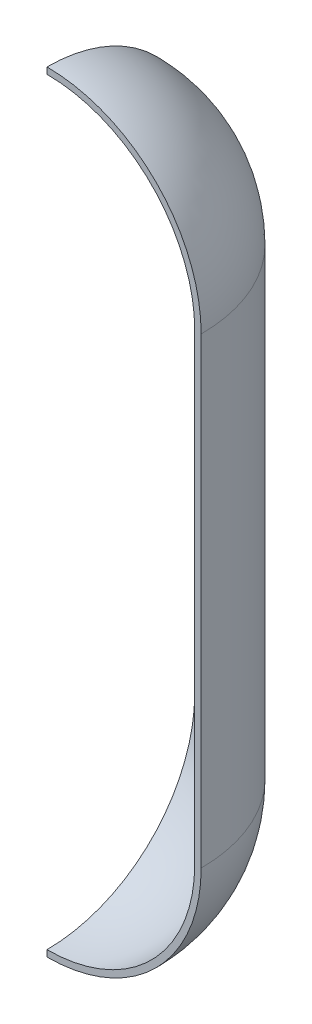
SolidWorks part; units mm, degrees
ref_plane "Front" through (0, 0, 0) normal (0, 0, 1) x (1, 0, 0)
ref_plane "Top" through (0, 0, 0) normal (0, 1, 0) x (1, 0, 0)
ref_plane "Right" through (0, 0, 0) normal (1, 0, 0) x (0, 0, -1)
other "Configuration Table"
sketch "Sketch1" plane through (0, 0, 0) normal (0, 0, 1) x (1, 0, 0)
  line L0 (0, 1258.6341) -> (0, -97.2801) construction
  line L1 (304.8, 0) -> (304.8, 914.4)
  line L2 (292.1, 0) -> (292.1, 914.4)
  line L3 (0, 1219.2) -> (0, 1206.5)
  line L4 (0, -292.1) -> (0, -304.8)
  arc A0 (304.8, 914.4) -> (0, 1219.2) centre (0, 914.4) ccw
  arc A1 (304.8, 0) -> (0, -304.8) centre (0, 0) cw
  arc A2 (292.1, 914.4) -> (0, 1206.5) centre (0, 914.4) ccw
  arc A3 (292.1, 0) -> (0, -292.1) centre (0, 0) cw
  dimension "D3" = 304.8
  dimension "D1" = 304.8
  dimension "D2" = 304.8
  dimension "D4" = 12.7
revolve "Revolve1" add sketch "Sketch1" angle 90 about L0 reverse direction yes
ref_axis "Axis1" through (0, 914.4, 0) along (0, -1, 0)
surface "Surface-MidSurface1" [suppressed] parameters "D0"=50000, "D2"=50000, "D1"=50000
equation "\"D3@Sketch1\" = \"D2@Sketch1\""
equation "\"D1@Sketch1\" = \"D2@Sketch1\""
